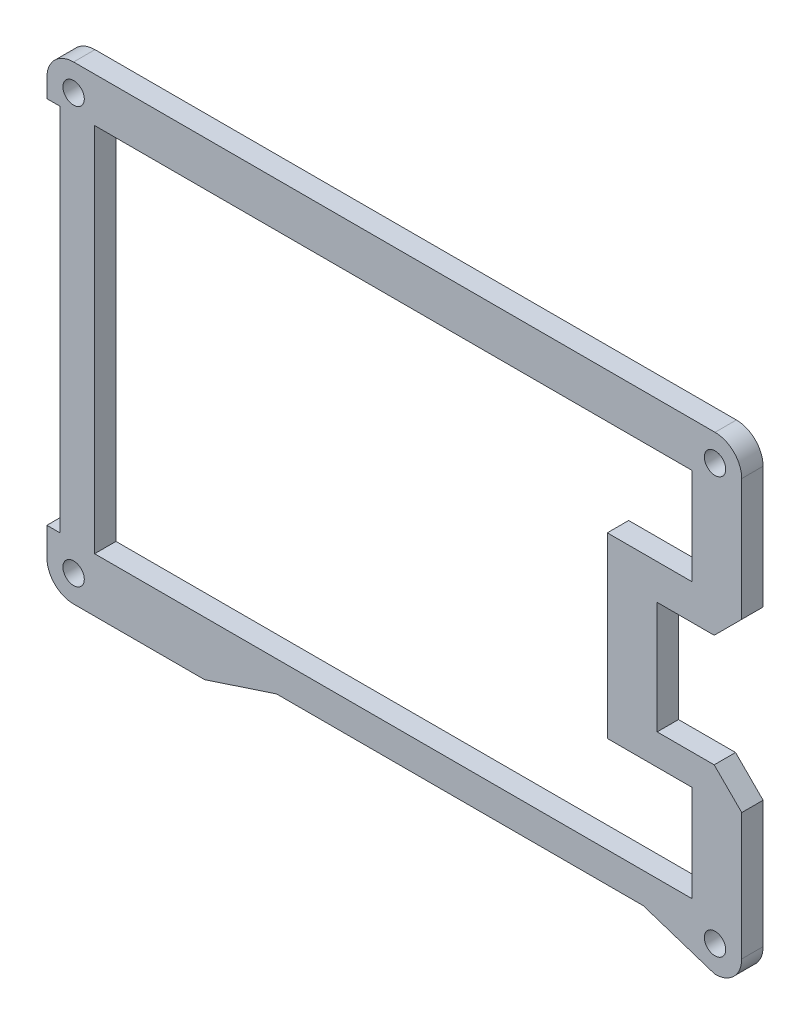
SolidWorks part; units mm, degrees
note: The reader was unsure of these and kept them because the rebuilt part matched: shared geometry of "Sketch4<4>".
ref_plane "Front Plane" through (0, 0, 0) normal (0, 0, 1) x (1, 0, 0)
ref_plane "Top Plane" through (0, 0, 0) normal (0, 1, 0) x (1, 0, 0)
ref_plane "Right Plane" through (0, 0, 0) normal (1, 0, 0) x (0, 0, -1)
sketch "Sketch1" plane through (0, 0, 0) normal (0, 0, 1) x (1, 0, 0)
  line L0 (-309.8086, 128.8851) -> (-305.8779, 128.8851) construction
  line L1 (-305.8779, 128.8851) -> (-301.9473, 132.8157) construction
  line L2 (-301.9473, 132.8157) -> (-301.9473, 150.9704) construction
  line L3 (-305.7573, 154.7804) -> (-397.2471, 154.7804) construction
  line L4 (-401.0571, 150.9566) -> (-401.0571, 148.341) construction
  line L5 (-401.0571, 148.341) -> (-399.1521, 148.341) construction
  line L6 (-399.1521, 148.341) -> (-399.1521, 95.6449) construction
  line L7 (-399.1521, 95.6449) -> (-401.0571, 95.6449) construction
  line L8 (-401.0571, 95.6449) -> (-401.0571, 91.6593) construction
  line L9 (-378.5565, 87.8217) -> (-397.2472, 87.8217) construction
  line L10 (-368.3165, 91.1883) -> (-378.5565, 87.8217) construction
  line L11 (-315.9973, 91.1883) -> (-368.3165, 91.1883) construction
  line L12 (-315.9973, 91.1883) -> (-305.7573, 87.8217) construction
  line L13 (-301.9473, 91.6317) -> (-301.9473, 111.7465) construction
  line L14 (-305.8779, 115.6771) -> (-301.9473, 111.7465) construction
  line L15 (-309.8086, 115.6771) -> (-305.8779, 115.6771) construction
  line L16 (-309.8086, 128.8851) -> (-305.8779, 128.8851)
  line L17 (-305.8779, 128.8851) -> (-301.9473, 132.8157)
  line L18 (-301.9473, 132.8157) -> (-301.9473, 150.9704)
  line L19 (-305.7573, 154.7804) -> (-397.2471, 154.7804)
  line L20 (-401.0571, 150.9566) -> (-401.0571, 148.341)
  line L21 (-401.0571, 148.341) -> (-399.1521, 148.341)
  line L22 (-399.1521, 148.341) -> (-399.1521, 95.6449)
  line L23 (-399.1521, 95.6449) -> (-401.0571, 95.6449)
  line L24 (-401.0571, 95.6449) -> (-401.0571, 91.6593)
  line L25 (-378.5565, 87.8217) -> (-397.2472, 87.8217)
  line L26 (-368.3165, 91.1883) -> (-378.5565, 87.8217)
  line L27 (-315.9973, 91.1883) -> (-368.3165, 91.1883)
  line L28 (-315.9973, 91.1883) -> (-305.7573, 87.8217)
  line L29 (-301.9473, 91.6317) -> (-301.9473, 111.7465)
  line L30 (-305.8779, 115.6771) -> (-301.9473, 111.7465)
  line L31 (-309.8086, 115.6771) -> (-305.8779, 115.6771)
  line L32 (-309.8086, 128.8851) -> (-314.0123, 128.8851)
  line L33 (-314.0123, 128.8851) -> (-314.0123, 115.6771)
  line L34 (-314.0123, 115.6771) -> (-309.8086, 115.6771)
  line L35 (-395.3675, 92.9525) -> (-395.3675, 149.2432) construction
  line L36 (-395.3675, 92.9525) -> (-395.3675, 149.2432)
  line L37 (-395.3675, 149.2432) -> (-309.8086, 149.2432) construction
  line L38 (-395.3675, 149.2432) -> (-309.8086, 149.2432)
  line L39 (-395.3675, 92.9525) -> (-309.8086, 92.9525) construction
  line L40 (-395.3675, 92.9525) -> (-309.8086, 92.9525)
  line L41 (-309.8086, 111.7465) -> (-318.2033, 111.7465)
  line L42 (-309.8086, 115.6771) -> (-309.8086, 92.9525) construction
  line L43 (-318.2033, 111.7465) -> (-318.2033, 132.8157)
  line L44 (-318.2033, 134.8668) -> (-318.2033, 116.6297) construction
  line L45 (-318.2033, 132.8157) -> (-309.8086, 132.8157)
  line L46 (-309.8086, 149.2432) -> (-309.8086, 128.8851) construction
  line L47 (-309.8086, 132.8157) -> (-309.8086, 149.2432)
  line L48 (-309.8086, 111.7465) -> (-309.8086, 92.9525)
  arc A0 (-301.9473, 150.9704) -> (-305.7573, 154.7804) centre (-305.7573, 150.9704) ccw construction
  arc A1 (-397.2471, 154.7804) -> (-401.0571, 150.9566) centre (-397.2471, 150.9704) ccw construction
  arc A2 (-401.0571, 91.6593) -> (-397.2472, 87.8217) centre (-397.2472, 91.6317) ccw construction
  arc A3 (-305.7573, 87.8217) -> (-301.9473, 91.6317) centre (-305.7573, 91.6317) ccw construction
  arc A4 (-301.9473, 150.9704) -> (-305.7573, 154.7804) centre (-305.7573, 150.9704) ccw
  arc A5 (-397.2471, 154.7804) -> (-401.0571, 150.9566) centre (-397.2471, 150.9704) ccw
  arc A6 (-401.0571, 91.6593) -> (-397.2472, 87.8217) centre (-397.2472, 91.6317) ccw
  arc A7 (-305.7573, 87.8217) -> (-301.9473, 91.6317) centre (-305.7573, 91.6317) ccw
  dimension "D1" = 12.065
extrude "Boss-Extrude1" add sketch "Sketch1" along normal blind 3.048
sketch "Sketch2" plane through (0, 0, 0) normal (0, 0, -1) x (-1, 0, 0)
  circle A0 centre (305.7573, 150.9704) radius 1.3559
  circle A1 centre (397.2471, 150.9704) radius 1.3559
  circle A2 centre (397.2472, 91.6317) radius 1.3559
  circle A3 centre (305.7573, 91.6317) radius 1.3559
  dimension "D1" = 2.7118
extrude "Cut-Extrude1" cut sketch "Sketch2" against normal through all
sketch "Sketch3" plane through (0, 0, 0) normal (0, 0, -1) x (-1, 0, 0)
  circle A0 centre (305.7573, 150.9704) radius 1.524
  circle A1 centre (397.2471, 150.9704) radius 1.524
  circle A2 centre (397.2472, 91.6317) radius 1.524
  circle A3 centre (305.7573, 91.6317) radius 1.524
  dimension "D1" = 3.048
extrude "Cut-Extrude2" cut sketch "Sketch3" against normal through all
sketch "Sketch4" plane through (0, 0, 3.048) normal (0, 0, 1) x (1, 0, 0)
  line L0 (-301.9473, 133.5777) -> (-305.8779, 129.6471)
  line L1 (-301.9473, 132.8157) -> (-301.9473, 150.9704) construction
  line L2 (-305.8779, 129.6471) -> (-314.0123, 129.6471)
  line L3 (-314.0123, 113.6451) -> (-305.8779, 113.6451)
  line L4 (-305.8779, 113.6451) -> (-301.9473, 109.7145)
  line L5 (-301.9473, 91.6317) -> (-301.9473, 111.7465) construction
  line L6 (-314.0123, 129.6471) -> (-314.0123, 113.6451)
  line L7 (-301.9473, 133.5777) -> (-301.9473, 109.7145)
  line L8 (-305.8779, 128.8851) -> (-301.9473, 132.8157) construction
  line L9 (-301.9473, 111.7465) -> (-305.8779, 115.6771) construction
  line L10 (-314.0123, 128.8851) -> (-305.8779, 128.8851) construction
  line L11 (-305.8779, 115.6771) -> (-314.0123, 115.6771) construction
  line L12 (-314.0123, 115.6771) -> (-314.0123, 128.8851) construction
  line L13 (-301.9473, 136.6257) -> (-305.8779, 132.6951)
  line L14 (-305.8779, 132.6951) -> (-318.2033, 132.6951)
  line L15 (-318.2033, 132.6951) -> (-318.2033, 110.5971)
  line L16 (-318.2033, 110.5971) -> (-305.8779, 110.5971)
  line L17 (-305.8779, 110.5971) -> (-301.9473, 106.6665)
  line L18 (-301.9473, 106.6665) -> (-301.9473, 109.7145)
  line L19 (-318.2033, 111.7465) -> (-318.2033, 132.8157) construction
  line L20 (-301.9473, 136.6257) -> (-301.9473, 133.5777)
  line M5 (-314.0123, 128.8851) -> (-305.8779, 128.8851)
  line M6 (-305.8779, 128.8851) -> (-301.9473, 132.8157)
  line M7 (-301.9473, 132.8157) -> (-301.9473, 150.9704)
  line M22 (-301.9473, 91.6317) -> (-301.9473, 111.7465)
  line M23 (-301.9473, 111.7465) -> (-305.8779, 115.6771)
  line M24 (-305.8779, 115.6771) -> (-314.0123, 115.6771)
  line M25 (-314.0123, 115.6771) -> (-314.0123, 128.8851)
  line M26 (-309.8086, 111.7465) -> (-309.8086, 92.9525)
  line M30 (-309.8086, 149.2432) -> (-309.8086, 132.8157)
  line M31 (-309.8086, 132.8157) -> (-318.2033, 132.8157)
  line M33 (-318.2033, 111.7465) -> (-309.8086, 111.7465)
  dimension "D1" = 15.24
  dimension "D2" = 13.97
  dimension "D3" = 3.048
  dimension "D4" = 3.048
extrude "Cut-Extrude3" cut sketch "Sketch4" against normal through all contours L7 M6 M5 M25 M24 M23 | L2 L6 L0 M5 M6 M7 | L6 L3 L4 M24 M33 M26 M22 M23
extrude "Boss-Extrude2" add sketch "Sketch4<4>" against normal up to vertex (3.048 mm away) contours L16 L17 L4 L3 M22 M26 | L15 L16 L3 L6 M26 M33 | L14 L15 M31 M30
sketch "Sketch4<4>" plane through (0, 0, 3.048) normal (0, 0, 1) x (1, 0, 0) same geometry as "Sketch4"
sketch "Sketch5" plane through (0, 0, 3.048) normal (0, 0, 1) x (1, 0, 0)
  line L0 (-305.7573, 154.7804) -> (-397.2471, 154.7804) construction
  line L1 (-394.2499, 148.4304) -> (-321.1243, 148.4304)
  line L2 (-394.2499, 148.4304) -> (-394.2499, 95.5317)
  line L3 (-394.2499, 95.5317) -> (-321.1243, 95.5317)
  line L4 (-321.1243, 148.4304) -> (-321.1243, 95.5317)
  line L5 (-368.3165, 91.1883) -> (-315.9973, 91.1883) construction
  line L6 (-399.1521, 148.341) -> (-399.1521, 95.6449) construction
  line L7 (-314.0123, 113.6451) -> (-314.0123, 129.6471) construction
  line L8 (-321.1243, 148.4304) -> (-312.1073, 148.4304)
  line L9 (-312.1073, 148.4304) -> (-312.1073, 134.681)
  line L10 (-312.1073, 134.681) -> (-321.1243, 134.681)
  line L11 (-321.1243, 95.5317) -> (-312.1073, 95.5317)
  line L12 (-312.1073, 95.5317) -> (-312.1073, 109.281)
  line L13 (-312.1073, 109.281) -> (-321.1243, 109.281)
  line L14 (-301.9473, 91.6317) -> (-301.9473, 109.7145) construction
  dimension "D1" = 6.35
  dimension "D2" = 4.3434
  dimension "D3" = 4.9022
  dimension "D4" = 7.112
  dimension "D5" = 10.16
  dimension "D6" = 25.4
extrude "Cut-Extrude4" cut sketch "Sketch5" against normal through all contours L4 L1 L2 L3 | L10 L9 L8 L4 | L12 L13 L4 L11
sketch "Sketch6" plane through (0, 0, 3.048) normal (0, 0, 1) x (1, 0, 0)
  line L0 (-312.1073, 148.4304) -> (-312.1073, 134.681) construction
  line L1 (-312.1073, 148.4304) -> (-309.0593, 148.4304)
  line L2 (-312.1073, 148.4304) -> (-312.1073, 134.681)
  line L3 (-312.1073, 134.681) -> (-309.0593, 134.681)
  line L4 (-309.0593, 148.4304) -> (-309.0593, 134.681)
  line L5 (-312.1073, 109.281) -> (-309.0593, 109.281)
  line L6 (-312.1073, 109.281) -> (-312.1073, 95.5317)
  line L7 (-312.1073, 95.5317) -> (-309.0593, 95.5317)
  line L8 (-309.0593, 109.281) -> (-309.0593, 95.5317)
  dimension "D1" = 3.048
  dimension "D2" = 3.048
extrude "Cut-Extrude5" cut sketch "Sketch6" against normal through all
